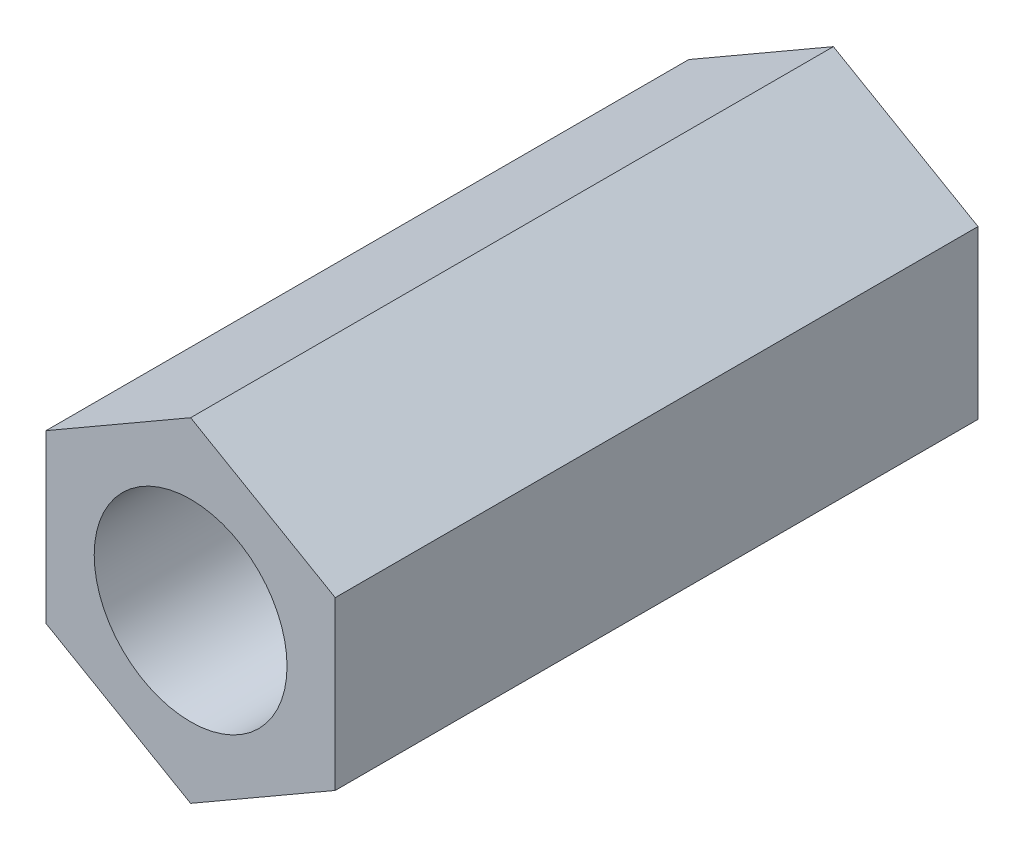
SolidWorks part; units mm, degrees
ref_plane "Front Plane" through (0, 0, 0) normal (0, 0, 1) x (1, 0, 0)
ref_plane "Top Plane" through (0, 0, 0) normal (0, 1, 0) x (1, 0, 0)
ref_plane "Right Plane" through (0, 0, 0) normal (1, 0, 0) x (0, 0, -1)
sketch "Sketch3" plane through (0, 0, 0) normal (1, 0, 0) x (0, 0, -1)
  line L0 (-5, 0) -> (5, 0) construction
  line L1 (0, 2.25) -> (0, -2.25) construction
  line L2 (-5, 1.5) -> (-5, -1.5) construction
  point P2 (0.2, 0)
  point P3 (-0.2, 0)
  dimension "D1" = 4.8
sketch "Sketch1" plane through (0, 0, 0) normal (0, 0, 1) x (1, 0, 0)
  line L1 (0, 2.5981) -> (-2.25, 1.299)
  line L2 (-2.25, 1.299) -> (-2.25, -1.299)
  line L3 (-2.25, -1.299) -> (0, -2.5981)
  line L4 (0, -2.5981) -> (2.25, -1.299)
  line L5 (2.25, -1.299) -> (2.25, 1.299)
  line L6 (2.25, 1.299) -> (0, 2.5981)
  circle A0 centre (0, 0) radius 2.25 construction
  circle A1 centre (0, 0) radius 1.5
extrude "Extrude1" add sketch "Sketch1" along normal up to vertex (5 mm away) and the other way up to vertex (5 mm away) up to point (0, 0, 5) other way up to point (0, 0, -5)
sketch "Sketch11" plane through (0, 0, -5) normal (0, 0, -1) x (-1, 0, 0)
  circle A0 centre (0, 0) radius 1.5 construction
  circle A1 centre (0, 0) radius 1.5
curve "Helix/Spiral1" [suppressed] pitch 0.5 height 10.5 turns 21 parameters "Pitch"=0.5
sketch "Sketch12" plane through (0, 0, 0) normal (1, 0, 0) x (0, 0, -1)
  line L0 (5.4375, 1.5) -> (5, 1.5)
  line L1 (5.4375, 1.5) -> (5.25, 1.1752)
  line L2 (5.25, 1.1752) -> (5.1875, 1.1752)
  line L3 (5.1875, 1.1752) -> (5, 1.5)
  line L4 (5.2188, 1.1752) -> (5.2188, 1.5) construction
  line L5 (5.3438, 1.3376) -> (5.0938, 1.3376) construction
  dimension "D1" = 0.0625
  dimension "D2" = 0.25
  dimension "D3" = 60
sweep "Sweep1" [suppressed] add profiles "Sketch12" path "Helix/Spiral1"
sketch "Sketch6" plane through (0, 0, -5) normal (0, 0, -1) x (-1, 0, 0)
  line L6 (0, 2.5981) -> (-2.25, 1.299)
  line L7 (-2.25, 1.299) -> (-2.25, -1.299)
  line L8 (-2.25, -1.299) -> (0, -2.5981)
  line L9 (0, -2.5981) -> (2.25, -1.299)
  line L10 (2.25, -1.299) -> (2.25, 1.299)
  line L11 (2.25, 1.299) -> (0, 2.5981)
  line L12 (0, 2.5981) -> (-2.25, 1.299)
  line L13 (-2.25, 1.299) -> (-2.25, -1.299)
  line L14 (-2.25, -1.299) -> (0, -2.5981)
  line L15 (0, -2.5981) -> (2.25, -1.299)
  line L16 (2.25, -1.299) -> (2.25, 1.299)
  line L17 (2.25, 1.299) -> (0, 2.5981)
  dimension "D1" = 0
extrude "Extrude2" [suppressed] cut sketch "Sketch6" along normal through all
sketch "Sketch7" plane through (0, 0, -5) normal (0, 0, -1) x (-1, 0, 0)
  circle A2 centre (0, 0) radius 1.5508
  circle A3 centre (0, 0) radius 1.5508
  dimension "D1" = 0.0508
extrude "Extrude3" [suppressed] cut sketch "Sketch7" against normal through all draft 43
sketch "Sketch8" plane through (0, 0, -5) normal (0, 0, -1) x (-1, 0, 0)
  circle A0 centre (0, 0) radius 2.25 construction
  circle A1 centre (0, 0) radius 2.25
extrude "Extrude4" [suppressed] cut sketch "Sketch8" against normal through all draft 60 flip side to cut
mirror "Mirror1" [suppressed] about plane through (0, 0, 0) normal (0, 0, 1)
sketch "Sketch9" [suppressed] plane through (0, 0, 0) normal (1, 0, 0) x (0, 0, -1)
  line L1 (-1.2, 1.1353) -> (1.2, 1.1353)
  line L2 (-1.2, 1.1353) -> (-1.2, 0)
  line L3 (-1.2, 0) -> (1.2, 0)
  line L4 (1.2, 1.1353) -> (1.2, 0)
  line L7 (-6, 0) -> (6, 0) construction
revolve "Revolve" [suppressed] add sketch "Sketch9" angle 360 about L0
sketch "Sketch10" [suppressed] plane through (0, 0, 0) normal (1, 0, 0) x (0, 0, -1)
  line L0 (6, 1.25) -> (1.2, 1.25)
  line L1 (-6, 1.25) -> (-1.2, 1.25)
  line L2 (1.2, 1.25) -> (1.2, -1.25)
  line L3 (-6, -1.25) -> (-1.2, -1.25)
  line L4 (-1.2, 1.25) -> (-1.2, -1.25)
  line L5 (1.2, -1.25) -> (6, -1.25)
equation "\"D1@Sketch3\" = \"Min Thread Length@Sketch3\""
equation "\"D3@Helix/Spiral1\" = \"Length@Sketch3\"+\"Pitch@Helix/Spiral1\""
equation "\"D1@Sketch12\" = \"Pitch@Helix/Spiral1\"*.125"
equation "\"D2@Sketch12\" = \"Pitch@Helix/Spiral1\"*.5"
